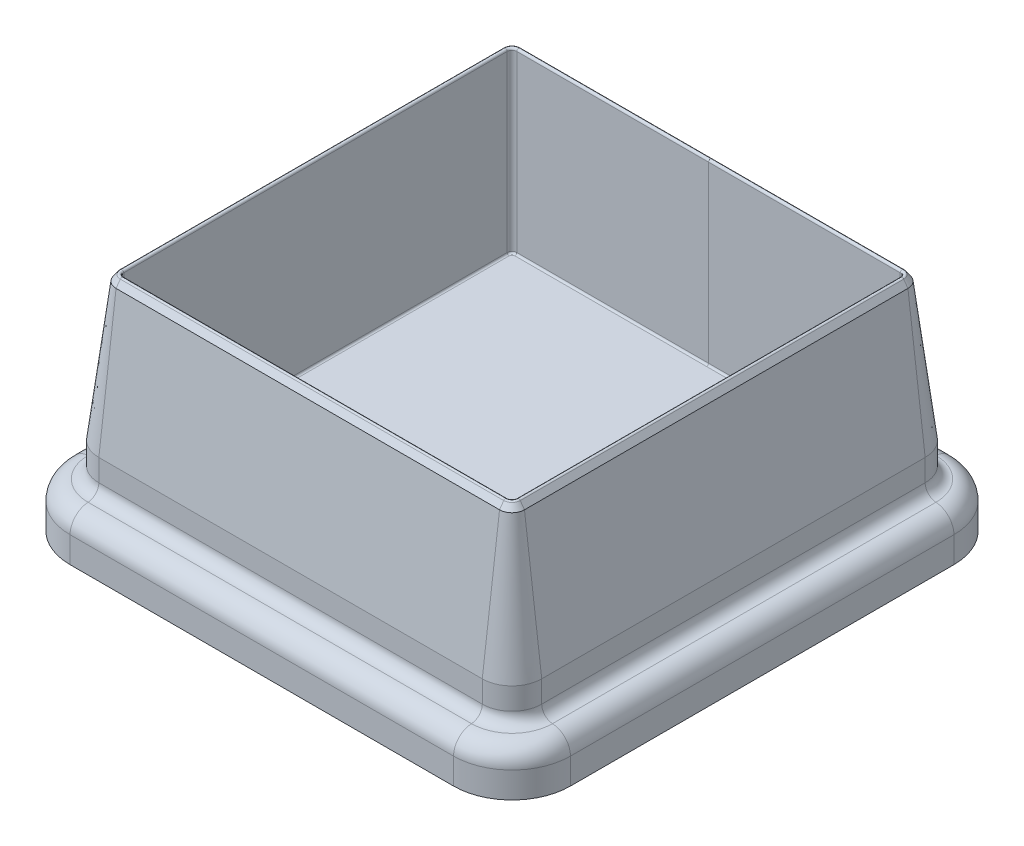
SolidWorks part; units mm, degrees
ref_plane "Front Plane" through (0, 0, 0) normal (0, 0, 1) x (1, 0, 0)
ref_plane "Top Plane" through (0, 0, 0) normal (0, 1, 0) x (1, 0, 0)
ref_plane "Right Plane" through (0, 0, 0) normal (1, 0, 0) x (0, 0, -1)
sketch "Sketch1" plane through (0, 0, 0) normal (0, 1, 0) x (1, 0, 0)
  line L0 (-28.575, 28.575) -> (28.575, -28.575) construction
  line L1 (-25.4, 28.575) -> (25.4, 28.575)
  line L2 (-28.575, 25.4) -> (-28.575, -25.4)
  line L3 (-25.4, -28.575) -> (25.4, -28.575)
  line L4 (28.575, 25.4) -> (28.575, -25.4)
  arc A0 (-25.4, -28.575) -> (-28.575, -25.4) centre (-25.4, -25.4) cw
  arc A1 (28.575, -25.4) -> (25.4, -28.575) centre (25.4, -25.4) cw
  arc A2 (-25.4, 28.575) -> (-28.575, 25.4) centre (-25.4, 25.4) ccw
  arc A3 (28.575, 25.4) -> (25.4, 28.575) centre (25.4, 25.4) ccw
  point P15 (28.575, 28.575)
  dimension "D2" = 3.175
  dimension "D3" = 3.175
  dimension "D4" = 3.175
  dimension "D1" = 57.15
sketch "Sketch2" plane through (0, 0, 0) normal (1, 0, 0) x (0, 0, -1)
  line L0 (27.051, 22.6808) -> (29.337, 4.4322)
  line L1 (29.337, 4.4322) -> (29.337, 0)
  line L2 (29.337, 0) -> (26.035, 0)
  line L4 (26.035, 24.13) -> (26.035, 0)
  spline S0 degree 1 poles (26.035, 24.13) (27.051, 22.6808) knots 0 0 1 1
  point P3 (28.575, 0)
sweep "Sweep1" add profiles "Sketch2" path "Sketch1"
sketch "Sketch3" plane through (0, 0, 0) normal (0, -1, 0) x (1, 0, 0)
  line L0 (-25.4, -29.337) -> (0, -29.337) construction
  line L1 (-29.337, 25.4) -> (-29.337, -25.4) construction
  line L2 (25.4, 29.337) -> (-25.4, 29.337) construction
  line L3 (0, -29.337) -> (25.4, -29.337) construction
  line L4 (29.337, -25.4) -> (29.337, 25.4) construction
  line L5 (-25.4, -29.337) -> (0, -29.337)
  line L6 (-29.337, 25.4) -> (-29.337, -25.4)
  line L7 (25.4, 29.337) -> (-25.4, 29.337)
  line L8 (0, -29.337) -> (25.4, -29.337)
  line L9 (29.337, -25.4) -> (29.337, 25.4)
  arc A0 (-29.337, -25.4) -> (-25.4, -29.337) centre (-25.4, -25.4) ccw construction
  arc A1 (-25.4, 29.337) -> (-29.337, 25.4) centre (-25.4, 25.4) ccw construction
  arc A2 (29.337, 25.4) -> (25.4, 29.337) centre (25.4, 25.4) ccw construction
  arc A3 (25.4, -29.337) -> (29.337, -25.4) centre (25.4, -25.4) ccw construction
  arc A4 (-29.337, -25.4) -> (-25.4, -29.337) centre (-25.4, -25.4) ccw
  arc A5 (-25.4, 29.337) -> (-29.337, 25.4) centre (-25.4, 25.4) ccw
  arc A6 (29.337, 25.4) -> (25.4, 29.337) centre (25.4, 25.4) ccw
  arc A7 (25.4, -29.337) -> (29.337, -25.4) centre (25.4, -25.4) ccw
extrude "Boss-Extrude1" add sketch "Sketch3" along normal blind 5.969
sketch "Sketch4" plane through (0, -5.969, 0) normal (0, -1, 0) x (1, 0, 0)
  line L8 (-25.4, -27.432) -> (25.4, -27.432)
  line L9 (27.432, -25.4) -> (27.432, 25.4)
  line L10 (25.4, 27.432) -> (-25.4, 27.432)
  line L11 (-27.432, 25.4) -> (-27.432, -25.4)
  line L12 (-25.4, -27.432) -> (25.4, -27.432)
  line L13 (27.432, -25.4) -> (27.432, 25.4)
  line L14 (25.4, 27.432) -> (-25.4, 27.432)
  line L15 (-27.432, 25.4) -> (-27.432, -25.4)
  arc A8 (-27.432, -25.4) -> (-25.4, -27.432) centre (-25.4, -25.4) ccw
  arc A9 (25.4, -27.432) -> (27.432, -25.4) centre (25.4, -25.4) ccw
  arc A10 (27.432, 25.4) -> (25.4, 27.432) centre (25.4, 25.4) ccw
  arc A11 (-25.4, 27.432) -> (-27.432, 25.4) centre (-25.4, 25.4) ccw
  arc A12 (-27.432, -25.4) -> (-25.4, -27.432) centre (-25.4, -25.4) ccw
  arc A13 (25.4, -27.432) -> (27.432, -25.4) centre (25.4, -25.4) ccw
  arc A14 (27.432, 25.4) -> (25.4, 27.432) centre (25.4, 25.4) ccw
  arc A15 (-25.4, 27.432) -> (-27.432, 25.4) centre (-25.4, 25.4) ccw
  dimension "D1" = 1.905
extrude "Cut-Extrude1" cut sketch "Sketch4" against normal blind 0.635
sketch "Sketch5" plane through (0, -5.969, 0) normal (0, -1, 0) x (1, 0, 0)
  line L0 (-29.337, 25.4) -> (-29.337, -25.4) construction
  line L1 (-25.4, -29.337) -> (25.4, -29.337) construction
  line L2 (25.4, 29.337) -> (-25.4, 29.337) construction
  line L3 (29.337, -25.4) -> (29.337, 25.4) construction
  line L4 (-29.337, 25.4) -> (-29.337, -25.4) construction
  line L5 (-25.4, -29.337) -> (25.4, -29.337) construction
  line L6 (25.4, 29.337) -> (-25.4, 29.337) construction
  line L7 (29.337, -25.4) -> (29.337, 25.4) construction
  line L8 (-33.147, 25.4) -> (-33.147, -25.4)
  line L9 (-25.4, -33.147) -> (25.4, -33.147)
  line L10 (33.147, -25.4) -> (33.147, 25.4)
  line L11 (25.4, 33.147) -> (-25.4, 33.147)
  line L12 (-27.432, 25.4) -> (-27.432, -25.4) construction
  line L13 (-25.4, -27.432) -> (25.4, -27.432) construction
  line L14 (25.4, 27.432) -> (-25.4, 27.432) construction
  line L15 (27.432, -25.4) -> (27.432, 25.4) construction
  line L16 (-27.432, 25.4) -> (-27.432, -25.4)
  line L17 (-25.4, -27.432) -> (25.4, -27.432)
  line L18 (25.4, 27.432) -> (-25.4, 27.432)
  line L19 (27.432, -25.4) -> (27.432, 25.4)
  arc A0 (-25.4, 29.337) -> (-29.337, 25.4) centre (-25.4, 25.4) ccw construction
  arc A1 (-29.337, -25.4) -> (-25.4, -29.337) centre (-25.4, -25.4) ccw construction
  arc A2 (25.4, -29.337) -> (29.337, -25.4) centre (25.4, -25.4) ccw construction
  arc A3 (29.337, 25.4) -> (25.4, 29.337) centre (25.4, 25.4) ccw construction
  arc A4 (-25.4, 29.337) -> (-29.337, 25.4) centre (-25.4, 25.4) ccw construction
  arc A5 (-29.337, -25.4) -> (-25.4, -29.337) centre (-25.4, -25.4) ccw construction
  arc A6 (25.4, -29.337) -> (29.337, -25.4) centre (25.4, -25.4) ccw construction
  arc A7 (29.337, 25.4) -> (25.4, 29.337) centre (25.4, 25.4) ccw construction
  arc A8 (-33.147, -25.4) -> (-25.4, -33.147) centre (-25.4, -25.4) ccw
  arc A9 (25.4, -33.147) -> (33.147, -25.4) centre (25.4, -25.4) ccw
  arc A10 (33.147, 25.4) -> (25.4, 33.147) centre (25.4, 25.4) ccw
  arc A11 (-25.4, 33.147) -> (-33.147, 25.4) centre (-25.4, 25.4) ccw
  arc A12 (-25.4, 27.432) -> (-27.432, 25.4) centre (-25.4, 25.4) ccw construction
  arc A13 (-27.432, -25.4) -> (-25.4, -27.432) centre (-25.4, -25.4) ccw construction
  arc A14 (25.4, -27.432) -> (27.432, -25.4) centre (25.4, -25.4) ccw construction
  arc A15 (27.432, 25.4) -> (25.4, 27.432) centre (25.4, 25.4) ccw construction
  arc A16 (-25.4, 27.432) -> (-27.432, 25.4) centre (-25.4, 25.4) ccw
  arc A17 (-27.432, -25.4) -> (-25.4, -27.432) centre (-25.4, -25.4) ccw
  arc A18 (25.4, -27.432) -> (27.432, -25.4) centre (25.4, -25.4) ccw
  arc A19 (27.432, 25.4) -> (25.4, 27.432) centre (25.4, 25.4) ccw
  dimension "D1" = 3.81
extrude "Boss-Extrude2" add sketch "Sketch5" against normal up to vertex (5.969 mm away) up to point (0, 0, 0)
fillet "Fillet4" radius 1.524 7 edges at (29.337, 0, 0) (28.1839, 0, 28.1839) (0, 0, 29.337) (-28.1839, 0, 28.1839) (-29.337, 0, 0) (-28.1839, 0, -28.1839) (28.1839, 0, -28.1839)
fillet "Fillet5" radius 2.54 7 edges at (-30.878, 0, -30.878) (-33.147, 0, 0) (-30.878, 0, 30.878) (0, 0, 33.147) (30.878, 0, 30.878) (33.147, 0, 0) (30.878, 0, -30.878)
fillet "Fillet3" radius 0.254 18 edges at (-25.849, 24.13, -25.849) (-26.035, 24.13, 0) (-25.849, 24.13, 25.849) (0, 24.13, 26.035) (25.849, 24.13, 25.849) (26.035, 24.13, 0) (25.849, 24.13, -25.849) (12.7, 24.13, -26.035) (-25.849, 0, 25.849) (0, 0, 26.035) (25.849, 0, 25.849) (26.035, 0, 0) (25.849, 0, -25.849) (12.7, 0, -26.035) (-12.7, 0, -26.035) (-25.849, 0, -25.849) (-12.7, 24.13, -26.035) (-26.035, 0, 0)
